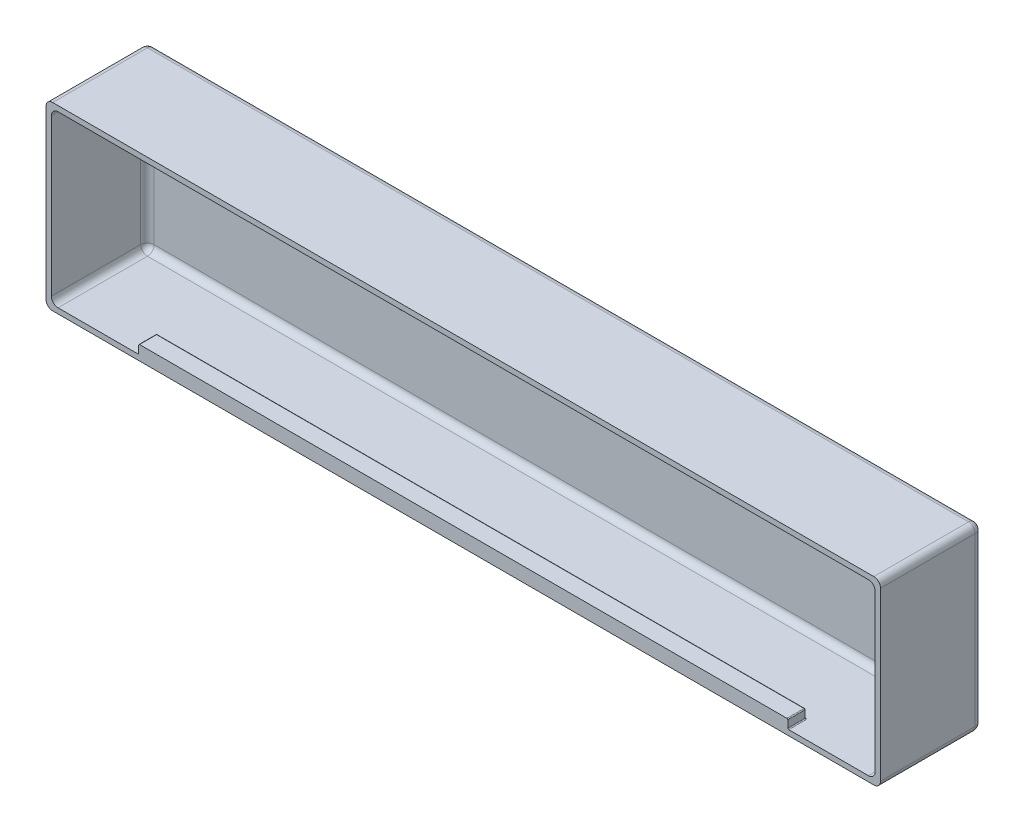
SolidWorks part; units mm, degrees
material "NEOPRENE"
ref_plane "Front" through (0, 0, 0) normal (0, 0, 1) x (1, 0, 0)
ref_plane "Top" through (0, 0, 0) normal (0, 1, 0) x (1, 0, 0)
ref_plane "Right" through (0, 0, 0) normal (1, 0, 0) x (0, 0, -1)
sketch "Sketch1" plane through (0, 0, 0) normal (0, 0, 1) x (1, 0, 0)
  line L1 (-118.618, -25.654) -> (118.618, -25.654)
  line L2 (-118.618, -25.654) -> (-118.618, 25.654)
  line L3 (-118.618, 25.654) -> (118.618, 25.654)
  line L4 (118.618, -25.654) -> (118.618, 25.654)
  line L5 (-118.618, -25.654) -> (118.618, 25.654) construction
  line L6 (-118.618, 25.654) -> (118.618, -25.654) construction
  point P0 (0, 0)
  dimension "D1" = 51.308
  dimension "D2" = 237.236
extrude "Boss-Extrude1" add sketch "Sketch1" along normal blind 28.829
shell "Shell1" thickness 1.524 removed face at (0, 0, 28.829)
fillet "Fillet1" radius 1.905 8 edges at (0, -24.13, 1.524) (-117.094, 0, 1.524) (0, 24.13, 1.524) (117.094, 0, 1.524) (117.094, -24.13, 15.1765) (117.094, 24.13, 15.1765) (-117.094, -24.13, 15.1765) (-117.094, 24.13, 15.1765)
fillet "Fillet2" radius 1.905 8 edges at (118.618, 0, 0) (-118.618, 0, 0) (0, 25.654, 0) (-118.618, 25.654, 14.4145) (-118.618, -25.654, 14.4145) (0, -25.654, 0) (118.618, -25.654, 14.4145) (118.618, 25.654, 14.4145)
sketch "Sketch2" plane through (0, 0, 0) normal (0, 0, -1) x (-1, 0, 0)
  circle A0 centre (-45.2, 1.571) radius 4.826
  circle A1 centre (45, 1.571) radius 4.826
  dimension "D1" = 9.652
extrude "Cut-Extrude1" cut sketch "Sketch2" against normal blind 2.54
sketch "Sketch3" plane through (0, -24.13, 0) normal (0, 1, 0) x (1, 0, 0)
  line L0 (0, -28.829) -> (0, 0) construction
  line L1 (-115.189, -28.829) -> (115.189, -28.829) construction
  line L3 (92.2655, -23.749) -> (-92.2655, -23.749)
  line L4 (92.2655, -23.749) -> (92.2655, -28.829)
  line L5 (92.2655, -28.829) -> (-92.2655, -28.829)
  line L6 (-92.2655, -23.749) -> (-92.2655, -28.829)
  line L7 (92.2655, -23.749) -> (-92.2655, -28.829) construction
  line L8 (92.2655, -28.829) -> (-92.2655, -23.749) construction
  point P5 (0, -26.289)
  dimension "D1" = 5.08
  dimension "D2" = 184.531
extrude "Boss-Extrude2" add sketch "Sketch3" along normal blind 2.54
fillet "Fillet3" radius 0.254 8 edges at (-92.2655, -22.86, 23.749) (-92.2655, -21.59, 26.289) (0, -21.59, 23.749) (92.2655, -21.59, 26.289) (92.2655, -24.13, 26.289) (-92.2655, -24.13, 26.289) (0, -24.13, 23.749) (92.2655, -22.86, 23.749)
sketch "Sketch4" [suppressed] plane through (0, 0, 0) normal (0, 0, -1) x (-1, 0, 0)
  line L0 (91.694, -5.9943) -> (59.8424, 12.3952) construction
  circle A0 centre (75.7682, 3.2005) radius 10.795
  dimension "D1" = 21.59
extrude "Cut-Extrude2" [suppressed] cut sketch "Sketch4" against normal blind 2.54
